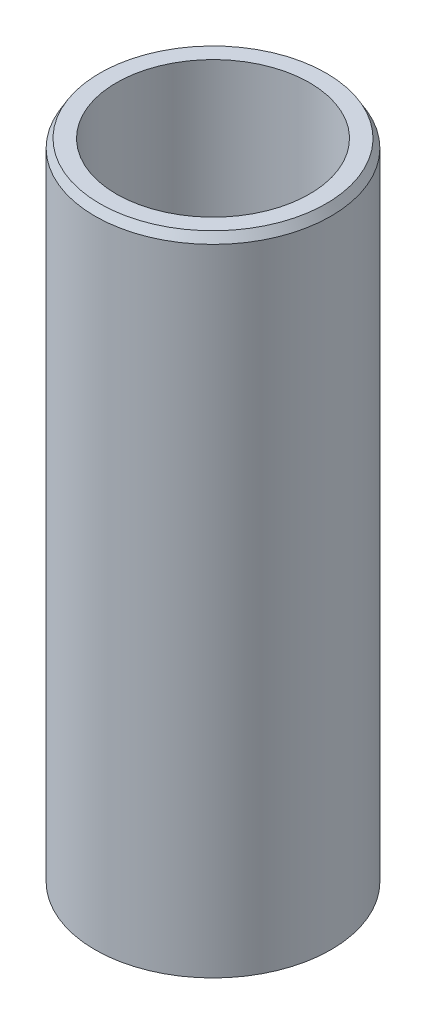
SolidWorks part; units mm, degrees
ref_plane "Front Plane" through (0, 0, 0) normal (0, 0, 1) x (1, 0, 0)
ref_plane "Top Plane" through (0, 0, 0) normal (0, 1, 0) x (1, 0, 0)
ref_plane "Right Plane" through (0, 0, 0) normal (1, 0, 0) x (0, 0, -1)
sketch "Sketch1" plane through (0, 0, 0) normal (0, 1, 0) x (1, 0, 0)
  circle A0 centre (0, 0) radius 57.5
  dimension "SHAFT_OD" = 115
extrude "Boss-Extrude1" add sketch "Sketch1" along normal blind 315.9767
sketch "Sketch2" plane through (0, 0, 0) normal (0, 1, 0) x (1, 0, 0)
  circle A0 centre (0, 0) radius 47.0345
  dimension "BORE_D" = 94.069
extrude "Cut-Extrude1" cut sketch "Sketch2" along normal through all
chamfer "Chamfer1" distance 4.0886 angle 30 2 edges at (0, 315.9767, 57.5) (0, 0, 57.5) first distance on face at (0, 315.9767, 57.5) first distance on face at (0, 0, 47.0345)
